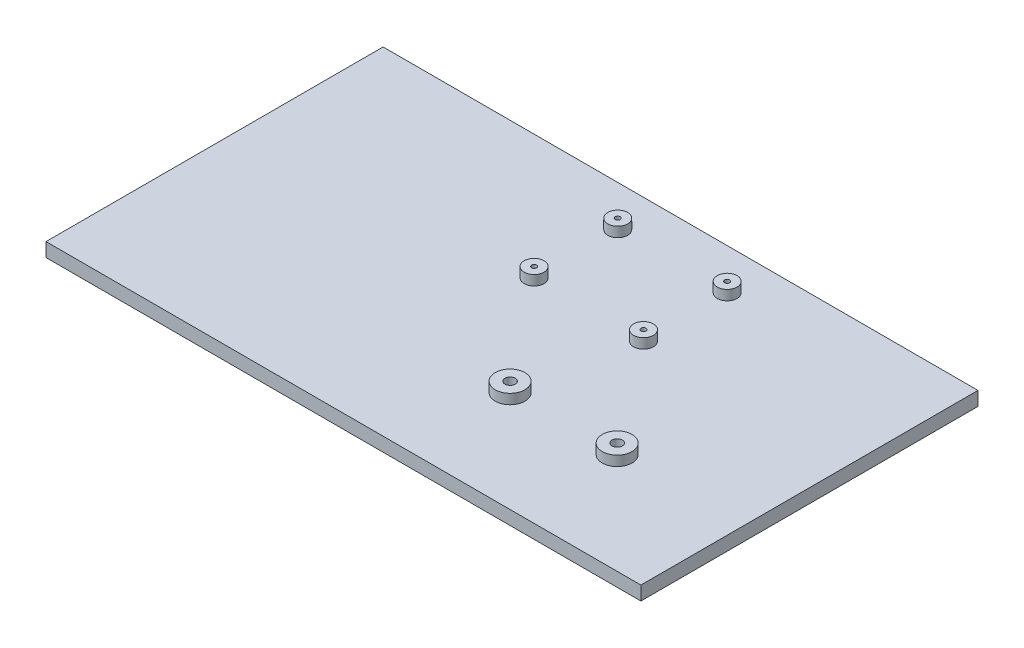
SolidWorks part; units mm, degrees
ref_plane "Front Plane" through (0, 0, 0) normal (0, 0, 1) x (1, 0, 0)
ref_plane "Top Plane" through (0, 0, 0) normal (0, 1, 0) x (1, 0, 0)
ref_plane "Right Plane" through (0, 0, 0) normal (1, 0, 0) x (0, 0, -1)
sketch "Sketch1" plane through (0, 0, 0) normal (0, 1, 0) x (1, 0, 0)
  line L1 (-150, -85) -> (150, -85)
  line L2 (-150, -85) -> (-150, 85)
  line L3 (-150, 85) -> (150, 85)
  line L4 (150, -85) -> (150, 85)
  line L5 (-150, -85) -> (150, 85) construction
  line L6 (-150, 85) -> (150, -85) construction
  point P0 (0, 0)
  dimension "D1" = 300
  dimension "D2" = 170
extrude "Boss-Extrude1" add sketch "Sketch1" along normal blind 7
sketch "12V-6V DC Converter" plane through (0, 7, 0) normal (0, 1, 0) x (1, 0, 0)
  line L0 (32.9875, -33.9552) -> (86.9875, -33.9552) construction
  line L1 (27.9875, -77.9552) -> (91.9875, -77.9552) construction
  line L2 (27.9875, -77.9552) -> (27.9875, -1.9552) construction
  line L3 (27.9875, -1.9552) -> (91.9875, -1.9552) construction
  line L4 (91.9875, -77.9552) -> (91.9875, -1.9552) construction
  line L5 (27.9875, -77.9552) -> (91.9875, -1.9552) construction
  line L6 (27.9875, -1.9552) -> (91.9875, -77.9552) construction
  circle A0 centre (32.9875, -33.9552) radius 3.25 construction
  circle A1 centre (86.9875, -33.9552) radius 2.5854 construction
  point P0 (59.9875, -39.9552)
  point P8 (0, 0)
  point P10 (-11.3713, -151.487)
  point P11 (59.9875, -33.9552)
  point P12 (0, 0)
  point P13 (12.8673, -111.9957)
  point P14 (0, 0)
  point P15 (31.4551, -68.7905)
  point P16 (59.9875, -39.9552)
  point P17 (0, 0)
  dimension "D4" = 6.5
  dimension "D1" = 76
  dimension "D2" = 64
  dimension "D3" = 27
  dimension "D5" = 32
sketch "Motor Driver" plane through (0, 7, 0) normal (0, 1, 0) x (1, 0, 0)
  line L1 (-203.2589, -53.9727) -> (-165.9789, -53.9727) construction
  line L2 (-203.2589, -53.9727) -> (-203.2589, -17.2327) construction
  line L3 (-203.2589, -17.2327) -> (-165.9789, -17.2327) construction
  line L4 (-165.9789, -53.9727) -> (-165.9789, -17.2327) construction
  line L5 (-203.2589, -53.9727) -> (-165.9789, -17.2327) construction
  line L6 (-203.2589, -17.2327) -> (-165.9789, -53.9727) construction
  line L7 (-206.1189, -57.1027) -> (-163.1189, -57.1027) construction
  line L8 (-206.1189, -57.1027) -> (-206.1189, -14.1027) construction
  line L9 (-206.1189, -14.1027) -> (-163.1189, -14.1027) construction
  line L10 (-163.1189, -57.1027) -> (-163.1189, -14.1027) construction
  line L11 (-206.1189, -57.1027) -> (-163.1189, -14.1027) construction
  line L12 (-206.1189, -14.1027) -> (-163.1189, -57.1027) construction
  circle A0 centre (-165.9789, -17.2327) radius 1.75 construction
  circle A1 centre (-203.2589, -17.2327) radius 1.75 construction
  circle A2 centre (-203.2589, -53.9727) radius 1.75 construction
  circle A3 centre (-165.9789, -53.9727) radius 1.75 construction
  point P0 (-184.6189, -35.6027)
  point P9 (-184.6189, -35.6027)
  point P14 (0, 0)
  dimension "D1" = 3.5
  dimension "D2" = 36.74
  dimension "D3" = 37.28
  dimension "D4" = 43
  dimension "D5" = 43
sketch "Battery" plane through (0, 7, 0) normal (0, 1, 0) x (1, 0, 0)
  line L1 (-278.642, 57.7634) -> (-158.642, 57.7634) construction
  line L2 (-278.642, 57.7634) -> (-278.642, 88.7634) construction
  line L3 (-278.642, 88.7634) -> (-158.642, 88.7634) construction
  line L4 (-158.642, 57.7634) -> (-158.642, 88.7634) construction
  line L5 (-278.642, 57.7634) -> (-158.642, 88.7634) construction
  line L6 (-278.642, 88.7634) -> (-158.642, 57.7634) construction
  point P0 (-218.642, 73.2634)
  dimension "D1" = 120
  dimension "D2" = 31
sketch "12V-5V converter" plane through (0, 7, 0) normal (0, 1, 0) x (1, 0, 0)
  line L0 (-299.6803, -107.0732) -> (-246.6803, -107.0732) construction
  line L1 (-304.6953, -127.8732) -> (-241.6653, -127.8732) construction
  line L2 (-304.6953, -127.8732) -> (-304.6953, -91.2732) construction
  line L3 (-304.6953, -91.2732) -> (-241.6653, -91.2732) construction
  line L4 (-241.6653, -127.8732) -> (-241.6653, -91.2732) construction
  line L5 (-304.6953, -127.8732) -> (-241.6653, -91.2732) construction
  line L6 (-304.6953, -91.2732) -> (-241.6653, -127.8732) construction
  circle A0 centre (-299.6803, -107.0732) radius 1.95 construction
  circle A1 centre (-246.6803, -107.0732) radius 1.95 construction
  point P0 (-273.1803, -109.5732)
  point P9 (-273.1803, -107.0732)
  point P10 (-289.8712, -115.2515)
  point P11 (-273.1803, -109.5732)
  dimension "D4" = 3.9
  dimension "D1" = 36.6
  dimension "D2" = 63.03
  dimension "D3" = 15.8
  dimension "D5" = 53
sketch "Raspberry pi4" plane through (0, 7, 0) normal (0, 1, 0) x (1, 0, 0)
  line L1 (-14.5588, 72.5414) -> (73.4412, 72.5414) construction
  line L2 (-14.5588, 72.5414) -> (-14.5588, 14.0414) construction
  line L3 (-14.5588, 14.0414) -> (73.4412, 14.0414) construction
  line L4 (73.4412, 72.5414) -> (73.4412, 14.0414) construction
  line L5 (-14.5588, 72.5414) -> (73.4412, 14.0414) construction
  line L6 (-14.5588, 14.0414) -> (73.4412, 72.5414) construction
  line L8 (-11.0588, 22.1951) -> (44.1162, 22.1951) construction
  line L9 (-11.0588, 22.1951) -> (-11.0588, 64.3878) construction
  line L10 (-11.0588, 64.3878) -> (44.1162, 64.3878) construction
  line L11 (44.1162, 22.1951) -> (44.1162, 64.3878) construction
  line L12 (-11.0588, 22.1951) -> (44.1162, 64.3878) construction
  line L13 (-11.0588, 64.3878) -> (44.1162, 22.1951) construction
  circle A0 centre (44.1162, 64.3878) radius 1.35 construction
  circle A1 centre (-11.0588, 64.3878) radius 1.35 construction
  circle A2 centre (-11.0588, 22.1951) radius 1.35 construction
  circle A3 centre (44.1162, 22.1951) radius 1.35 construction
  point P0 (29.4412, 43.2914)
  point P8 (16.5287, 43.2914)
  point P14 (12.121, 42.3549)
  point P15 (0, 0)
  point P16 (0, 0)
  point P17 (16.5287, 43.2914)
  dimension "D3" = 2.7
  dimension "D1" = 88
  dimension "D2" = 58.5
  dimension "D4" = 3.5
sketch "Sketch9" plane through (0, 7, 0) normal (0, 1, 0) x (1, 0, 0)
  circle A0 centre (-11.0588, 64.3878) radius 5
  circle A1 centre (44.1162, 64.3878) radius 5
  circle A2 centre (44.1162, 22.1951) radius 5
  circle A3 centre (-11.0588, 22.1951) radius 5
  dimension "D1" = 10
extrude "Boss-Extrude2" add sketch "Sketch9" along normal blind 5
sketch "Sketch8" plane through (0, 7, 0) normal (0, 1, 0) x (1, 0, 0)
  circle A0 centre (44.1162, 22.1951) radius 1.25
  circle A1 centre (-11.0588, 22.1951) radius 1.25
  circle A2 centre (-11.0588, 64.3878) radius 1.25
  circle A3 centre (44.1162, 64.3878) radius 1.25
  dimension "D1" = 2.5
extrude "Cut-Extrude1" cut sketch "Sketch8" against normal through all both and the other way through all
sketch "Sketch10" plane through (0, 7, 0) normal (0, 1, 0) x (1, 0, 0)
  circle A0 centre (32.9875, -33.9552) radius 7.5
  circle A1 centre (86.9875, -33.9552) radius 7.5
  dimension "D1" = 15
extrude "Boss-Extrude3" add sketch "Sketch10" along normal blind 5
sketch "Sketch11" plane through (0, 12, 0) normal (0, 1, 0) x (1, 0, 0)
  circle A0 centre (32.9875, -33.9552) radius 2.6
  circle A1 centre (86.9875, -33.9552) radius 2.6
  dimension "D1" = 5.2
extrude "Cut-Extrude2" cut sketch "Sketch11" against normal through all
